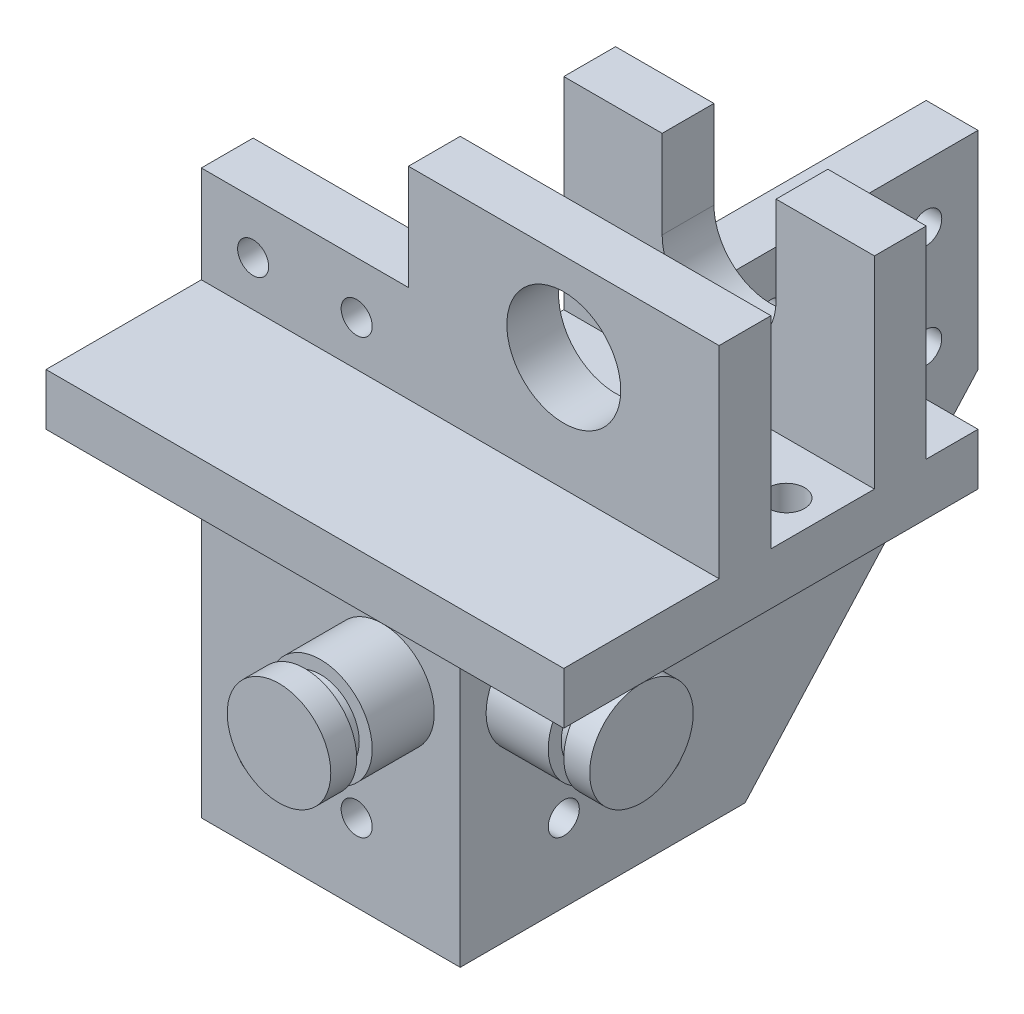
SolidWorks part; units mm, degrees
ref_plane "Front Plane" through (0, 0, 0) normal (0, 0, 1) x (1, 0, 0)
ref_plane "Top Plane" through (0, 0, 0) normal (0, 1, 0) x (1, 0, 0)
ref_plane "Right Plane" through (0, 0, 0) normal (1, 0, 0) x (0, 0, -1)
sketch "Sketch1" plane through (0, 0, 0) normal (0, 1, 0) x (1, 0, 0)
  line L0 (0, 0) -> (100, 0)
  line L1 (100, 0) -> (100, 80)
  line L2 (100, 80) -> (40, 80)
  line L3 (40, 80) -> (40, 40)
  line L4 (40, 40) -> (0, 40)
  line L5 (0, 40) -> (0, 0)
  dimension "D1" = 40
  dimension "D2" = 40
  dimension "D3" = 80
  dimension "D4" = 100
extrude "Boss-Extrude1" add sketch "Sketch1" along normal blind 10
sketch "Sketch2" plane through (0, 10, 0) normal (0, 1, 0) x (1, 0, 0)
  line L0 (40, 80) -> (40, 40) construction
  line L1 (0, 40) -> (40, 40)
  line L2 (0, 40) -> (0, 30)
  line L3 (0, 30) -> (40, 30)
  line L4 (40, 40) -> (40, 30)
  dimension "D1" = 10
extrude "Boss-Extrude2" add sketch "Sketch2" along normal blind 18.71
sketch "Sketch3" plane through (0, 0, 0) normal (0, -1, 0) x (1, 0, 0)
  line L0 (0, -30) -> (50, -30)
  line L1 (0, -40) -> (0, 0) construction
  line L2 (50, -30) -> (50, -80)
  line L3 (100, -80) -> (40, -80) construction
  line L4 (50, -80) -> (40, -80)
  line L5 (40, -80) -> (40, -40)
  line L6 (40, -40) -> (0, -40)
  line L7 (0, -40) -> (0, -30)
  dimension "D1" = 10
  dimension "D2" = 10
extrude "Boss-Extrude3" add sketch "Sketch3" along normal blind 80
sketch "Sketch5" plane through (0, 0, -80) normal (0, 0, -1) x (-1, 0, 0)
  line L1 (-40, 10) -> (-50, 10)
  line L2 (-40, 10) -> (-40, -80)
  line L3 (-40, -80) -> (-50, -80)
  line L4 (-50, 10) -> (-50, -80)
extrude "Boss-Extrude4" add sketch "Sketch5" along normal blind 50
sketch "Sketch6" plane through (40, 0, 0) normal (-1, 0, 0) x (0, 0, 1)
  line L0 (-85, 10) -> (-85, -80) construction
  line L1 (-130, 10) -> (-40, 10) construction
  line L2 (-40, -80) -> (-130, -80) construction
  line L3 (-85, -80) -> (-130, -30)
  line L4 (-130, -80) -> (-130, 10) construction
  line L5 (-130, -30) -> (-130, -80)
  line L6 (-130, -80) -> (-85, -80)
  dimension "D1" = 50
extrude "Cut-Extrude1" cut sketch "Sketch6" against normal blind 10
sketch "Sketch7" plane through (0, 10, 0) normal (0, 1, 0) x (1, 0, 0)
  line L0 (40, 130) -> (40, 40) construction
  line L1 (40, 70) -> (100, 70)
  line L2 (40, 70) -> (40, 60)
  line L3 (40, 60) -> (100, 60)
  line L4 (100, 70) -> (100, 60)
  line L5 (100, 0) -> (100, 80) construction
  line L6 (0, 0) -> (100, 0) construction
  line L7 (40, 40) -> (100, 40)
  line L8 (40, 40) -> (40, 30)
  line L9 (40, 30) -> (100, 30)
  line L10 (100, 40) -> (100, 30)
  dimension "D1" = 10
  dimension "D2" = 10
  dimension "D3" = 40
  dimension "D4" = 20
extrude "Boss-Extrude5" add sketch "Sketch7" along normal blind 39
sketch "Sketch8" plane through (0, 10, 0) normal (0, 1, 0) x (1, 0, 0)
  line L0 (100, 40) -> (100, 60) construction
  line L1 (100, 80) -> (50, 80) construction
  circle A0 centre (47, 50) radius 3.5
  circle A1 centre (93, 50) radius 3.5
  point P4 (0, 0)
  dimension "D2" = 7
  dimension "D1" = 7
  dimension "D3" = 46
  dimension "D4" = 30
extrude "Cut-Extrude2" cut sketch "Sketch8" against normal blind 10
sketch "Sketch9" plane through (50, 0, 0) normal (1, 0, 0) x (0, 0, -1)
  line L0 (50, 0) -> (57, 0)
  line L1 (51.8028, 0) -> (48.1972, 0) construction
  line L2 (80, 0) -> (51.8028, 0) construction
  line L3 (57, 0) -> (57, -6)
  line L4 (57, -6) -> (43, -6)
  line L5 (43, -6) -> (43, 0)
  line L6 (0, 0) -> (80, 0) construction
  line L8 (43, 0) -> (50, 0)
  dimension "D1" = 6
  dimension "D2" = 14
  dimension "D3" = 7
extrude "Cut-Extrude3" cut sketch "Sketch9" against normal blind 10
sketch "Sketch10" plane through (0, 0, -30) normal (0, 0, 1) x (1, 0, 0)
  line L0 (0, 10) -> (100, 10) construction
  line L1 (100, 49) -> (100, 10) construction
  line L2 (0, 28.71) -> (0, 10) construction
  line L3 (0, 28.71) -> (40, 28.71) construction
  line L4 (0, 0) -> (100, 0) construction
  line L5 (50, -80) -> (0, -80) construction
  circle A0 centre (70, 32) radius 11
  circle A1 centre (30, 18.71) radius 3
  circle A2 centre (10, 18.71) radius 3
  circle A3 centre (30, -15) radius 3
  circle A4 centre (10, -15) radius 3
  circle A5 centre (30, -65) radius 3
  circle A6 centre (10, -65) radius 3
  point P18 (0, 0)
  point P19 (0, 0)
  point P20 (0, 0)
  point P21 (0, 0)
  point P22 (0, 0)
  dimension "D1" = 22
  dimension "D4" = 6
  dimension "D2" = 22
  dimension "D3" = 30
  dimension "D5" = 20
  dimension "D6" = 10
  dimension "D7" = 10
  dimension "D8" = 15
  dimension "D9" = 15
extrude "Cut-Extrude4" cut sketch "Sketch10" against normal blind 10
sketch "Sketch11" plane through (50, 0, 0) normal (1, 0, 0) x (0, 0, -1)
  line L0 (30, -80) -> (30, 0) construction
  line L1 (85, -80) -> (30, -80) construction
  line L2 (0, 0) -> (80, 0) construction
  line L3 (130, 10) -> (130, -30) construction
  line L4 (80, 10) -> (80, 0) construction
  line L5 (130, 10) -> (80, 10) construction
  circle A0 centre (50, -15) radius 3
  circle A1 centre (70, -15) radius 3
  circle A4 centre (70, -65) radius 3
  circle A5 centre (50, -65) radius 3
  circle A6 centre (90, -1.3) radius 3
  circle A7 centre (120, -1.3) radius 3
  circle A8 centre (90, -21.3) radius 3
  circle A9 centre (120, -21.3) radius 3
  point P22 (0, 0)
  point P23 (0, 0)
  point P24 (0, 0)
  point P25 (0, 0)
  dimension "D1" = 6
  dimension "D6" = 6
  dimension "D2" = 20
  dimension "D3" = 20
  dimension "D4" = 15
  dimension "D5" = 15
  dimension "D7" = 20
  dimension "D8" = 10
  dimension "D9" = 10
  dimension "D10" = 11.3
extrude "Cut-Extrude5" cut sketch "Sketch11" against normal blind 10
sketch "Sketch12" plane through (0, 0, -70) normal (0, 0, -1) x (-1, 0, 0)
  line L0 (-70, 49) -> (-59, 49)
  line L1 (-100, 49) -> (-40, 49) construction
  line L2 (-59, 49) -> (-59, 32)
  line L3 (-70, 49) -> (-81, 49)
  line L4 (-81, 49) -> (-81, 32)
  line L5 (-100, 10) -> (-50, 10) construction
  arc A0 (-59, 32) -> (-81, 32) centre (-70, 32) cw
  point P9 (0, 0)
  point P11 (-81, 32)
  point P12 (-70, 31.9669)
  point P13 (-81, 32)
  point P14 (-59, 32)
  dimension "D1" = 11
  dimension "D2" = 22
  dimension "D3" = 11
  dimension "D4" = 11
extrude "Cut-Extrude6" cut sketch "Sketch12" against normal blind 10
sketch "Sketch13" plane through (50, 0, 0) normal (1, 0, 0) x (0, 0, -1)
  line L0 (30, -80) -> (30, 0) construction
  line L1 (85, -80) -> (30, -80) construction
  circle A0 centre (45, -40) radius 10
  dimension "D3" = 20
  dimension "D1" = 15
  dimension "D2" = 40
extrude "Boss-Extrude6" add sketch "Sketch13" along normal blind 20
sketch "Sketch14" plane through (70, 0, 0) normal (1, 0, 0) x (0, 0, -1)
  circle A0 centre (45, -40) radius 10
  circle A1 centre (45, -40) radius 7.5
  dimension "D1" = 20
  dimension "D2" = 15
extrude "Cut-Extrude7" cut sketch "Sketch14" against normal blind 3 from offset 5 offset against normal yes
sketch "Sketch15" plane through (0, 0, -30) normal (0, 0, 1) x (1, 0, 0)
  line L0 (50, -80) -> (50, 0) construction
  line L1 (50, -80) -> (0, -80) construction
  circle A0 centre (35, -40) radius 10
  dimension "D3" = 20
  dimension "D1" = 15
  dimension "D2" = 40
extrude "Boss-Extrude7" add sketch "Sketch15" along normal blind 20
sketch "Sketch16" plane through (0, 0, -10) normal (0, 0, 1) x (1, 0, 0)
  circle A0 centre (35, -40) radius 10
  circle A1 centre (35, -40) radius 7.5
  dimension "D1" = 20
  dimension "D2" = 15
extrude "Cut-Extrude8" cut sketch "Sketch16" against normal blind 3 from offset 5 offset against normal yes
